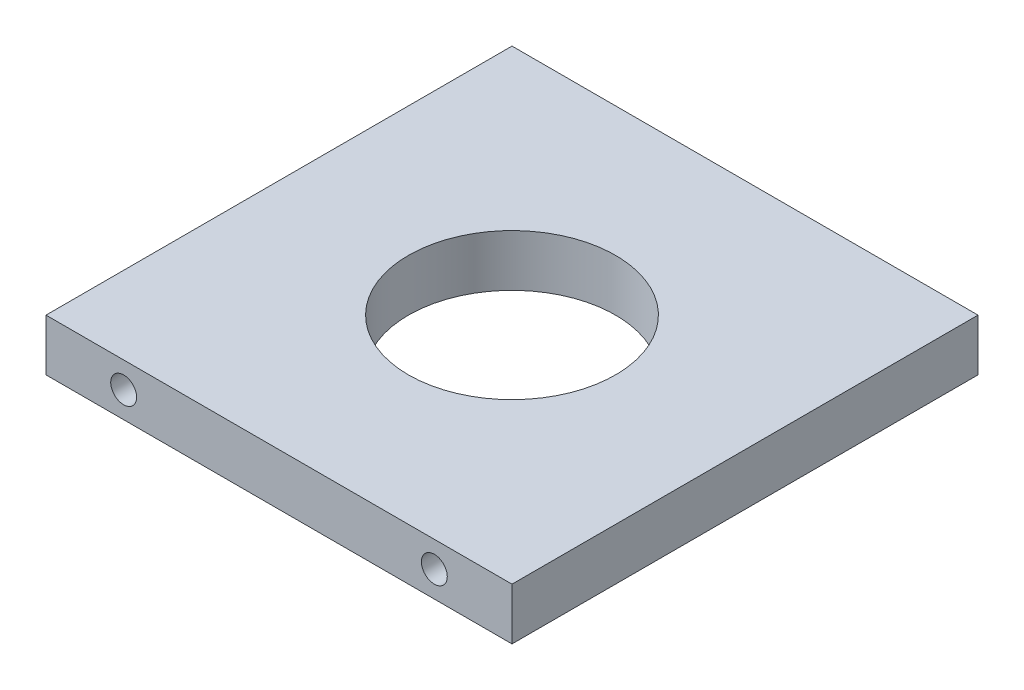
SolidWorks part; units mm, degrees
ref_plane "Front Plane" through (0, 0, 0) normal (0, 0, 1) x (1, 0, 0)
ref_plane "Top Plane" through (0, 0, 0) normal (0, 1, 0) x (1, 0, 0)
ref_plane "Right Plane" through (0, 0, 0) normal (1, 0, 0) x (0, 0, -1)
sketch "Sketch1" plane through (0, 0, 0) normal (0, 1, 0) x (1, 0, 0)
  line L1 (28.575, -28.575) -> (-28.575, -28.575)
  line L2 (28.575, -28.575) -> (28.575, 28.575)
  line L3 (28.575, 28.575) -> (-28.575, 28.575)
  line L4 (-28.575, -28.575) -> (-28.575, 28.575)
  line L5 (28.575, -28.575) -> (-28.575, 28.575) construction
  line L6 (28.575, 28.575) -> (-28.575, -28.575) construction
  circle A0 centre (0, 0) radius 12.7
  point P0 (0, 0)
  dimension "D2" = 25.4
  dimension "D1" = 57.15
extrude "Boss-Extrude1" add sketch "Sketch1" along normal blind 6.35
sketch "Sketch2" plane through (0, 0, 28.575) normal (0, 0, 1) x (1, 0, 0)
  line L0 (0, 0) -> (0, 6.35) construction
  line L3 (-28.575, 0) -> (28.575, 0) construction
  line L4 (-28.575, 6.35) -> (28.575, 6.35) construction
  line L5 (-19.05, 3.175) -> (19.05, 3.175) construction
  circle A0 centre (-19.05, 3.175) radius 1.5875
  circle A1 centre (19.05, 3.175) radius 1.5875
  point P10 (0, 3.175)
  point P11 (0, 0)
  dimension "D2" = 3.175
  dimension "D1" = 38.1
extrude "Cut-Extrude1" cut sketch "Sketch2" against normal blind 12.7
